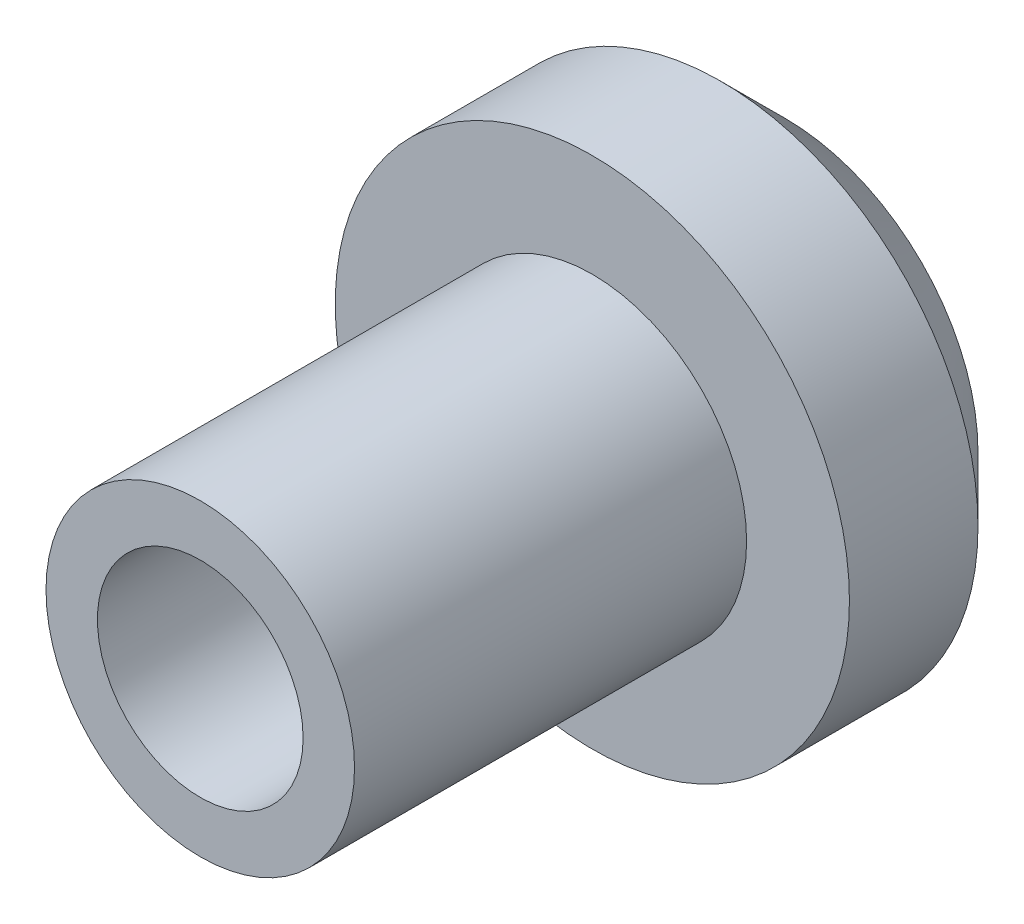
SolidWorks part; units mm, degrees
material "Copper"
ref_plane "Front Plane" through (0, 0, 0) normal (0, 0, 1) x (1, 0, 0)
ref_plane "Top Plane" through (0, 0, 0) normal (0, 1, 0) x (1, 0, 0)
ref_plane "Right Plane" through (0, 0, 0) normal (1, 0, 0) x (0, 0, -1)
sketch "Sketch1" plane through (0, 0, 0) normal (0, 0, 1) x (1, 0, 0)
  circle A0 centre (0, 0) radius 4
  dimension "D1" = 8
extrude "Boss-Extrude1" add sketch "Sketch1" along normal blind 3
sketch "Sketch2" plane through (0, 0, 3) normal (0, 0, 1) x (1, 0, 0)
  circle A0 centre (0, 0) radius 2.4
  dimension "D1" = 4.8
extrude "Boss-Extrude2" add sketch "Sketch2" along normal blind 6.1
sketch "Sketch3" plane through (0, 0, 9.1) normal (0, 0, 1) x (1, 0, 0)
  circle A0 centre (0, 0) radius 1.6
  dimension "D1" = 3.2
extrude "Cut-Extrude1" cut sketch "Sketch3" against normal through all
chamfer "Chamfer1" distance 1 angle 45 1 edges at (4, 0, 0)
